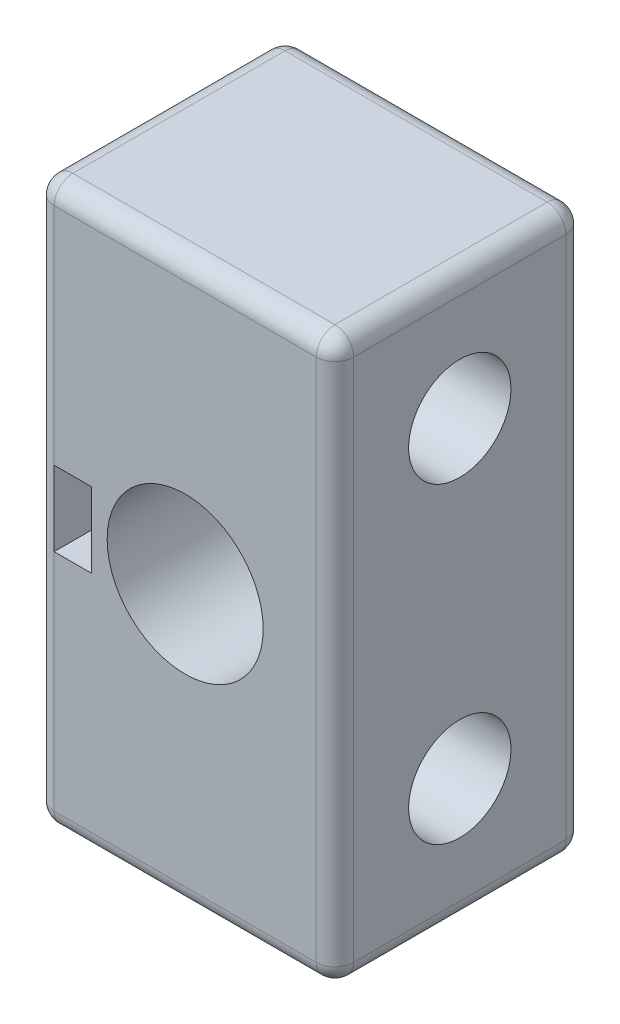
SolidWorks part; units mm, degrees
ref_plane "Front Plane" through (0, 0, 0) normal (0, 0, 1) x (1, 0, 0)
ref_plane "Top Plane" through (0, 0, 0) normal (0, 1, 0) x (1, 0, 0)
ref_plane "Right Plane" through (0, 0, 0) normal (1, 0, 0) x (0, 0, -1)
sketch "Sketch1" plane through (0, 0, 0) normal (0, 0, 1) x (1, 0, 0)
  line L1 (12, -22.5) -> (-12, -22.5)
  line L2 (12, -22.5) -> (12, 22.5)
  line L3 (12, 22.5) -> (-12, 22.5)
  line L4 (-12, -22.5) -> (-12, 22.5)
  line L5 (12, -22.5) -> (-12, 22.5) construction
  line L6 (12, 22.5) -> (-12, -22.5) construction
  point P0 (0, 0)
  dimension "D1" = 24
  dimension "D2" = 45
extrude "Extrude1" add sketch "Sketch1" along normal blind 20
sketch "Sketch2" plane through (12, 0, 0) normal (1, 0, 0) x (0, 0, -1)
  line L0 (0, 0) -> (-38.5346, 0) construction
  line L1 (0, -22.5) -> (0, 22.5) construction
  circle A0 centre (-10, 12.5) radius 4.1
  circle A1 centre (-10, -12.5) radius 4.1
  dimension "D1" = 8.2
  dimension "D2" = 12.5
  dimension "D3" = 10
extrude "Extrude2" cut sketch "Sketch2" against normal through all
sketch "Sketch3" plane through (0, 0, 20) normal (0, 0, 1) x (1, 0, 0)
  circle A0 centre (0, 0) radius 6.25
  dimension "D1" = 12.5
extrude "Extrude3" cut sketch "Sketch3" against normal blind 18
sketch "Sketch4" plane through (0, 0, 2) normal (0, 0, 1) x (1, 0, 0)
  circle A0 centre (0, 0) radius 4.75
  dimension "D1" = 9.5
extrude "Extrude4" cut sketch "Sketch4" against normal blind 18
sketch "Sketch5" plane through (0, 0, 20) normal (0, 0, 1) x (1, 0, 0)
  line L0 (0, 0) -> (-21.937, 0) construction
  line L2 (-10.5, -3) -> (-7.5, -3)
  line L3 (-10.5, -3) -> (-10.5, 3)
  line L4 (-10.5, 3) -> (-7.5, 3)
  line L5 (-7.5, -3) -> (-7.5, 3)
  line L6 (-10.5, -3) -> (-7.5, 3) construction
  line L7 (-10.5, 3) -> (-7.5, -3) construction
  point P3 (-9, 0)
  dimension "D1" = 6
  dimension "D2" = 3
  dimension "D3" = 9
extrude "Extrude5" cut sketch "Sketch5" against normal blind 14
sketch "Sketch6" plane through (-12, 0, 0) normal (-1, 0, 0) x (0, 0, 1)
  line L0 (10, 16.6) -> (10, -16.6) construction
  line L2 (13.04, 0) -> (11.52, 2.6327) construction
  line L3 (11.52, 2.6327) -> (8.48, 2.6327) construction
  line L4 (8.48, 2.6327) -> (6.96, 0) construction
  line L5 (6.96, 0) -> (8.48, -2.6327) construction
  line L6 (8.48, -2.6327) -> (11.52, -2.6327) construction
  line L7 (11.52, -2.6327) -> (13.04, 0) construction
  circle A0 centre (10, 12.5) radius 4.1 construction
  circle A1 centre (10, -12.5) radius 4.1 construction
  circle A2 centre (10, 0) radius 3.04 construction
  circle A3 centre (10, 0) radius 1.5
  dimension "D1" = 3
extrude "Extrude6" cut sketch "Sketch6" against normal blind 13
fillet "Fillet1" radius 1.5 12 edges at (-12, -22.5, 10) (0, -22.5, 20) (12, -22.5, 10) (0, -22.5, 0) (12, 22.5, 10) (0, 22.5, 20) (-12, 22.5, 10) (0, 22.5, 0) (-12, 0, 20) (12, 0, 20) (12, 0, 0) (-12, 0, 0)
fillet "Fillet2" radius 0.5 1 edges at (4.75, 0, 2)
fillet "Fillet3" radius 3 2 edges at (-9, -3, 6) (-9, 3, 6)
